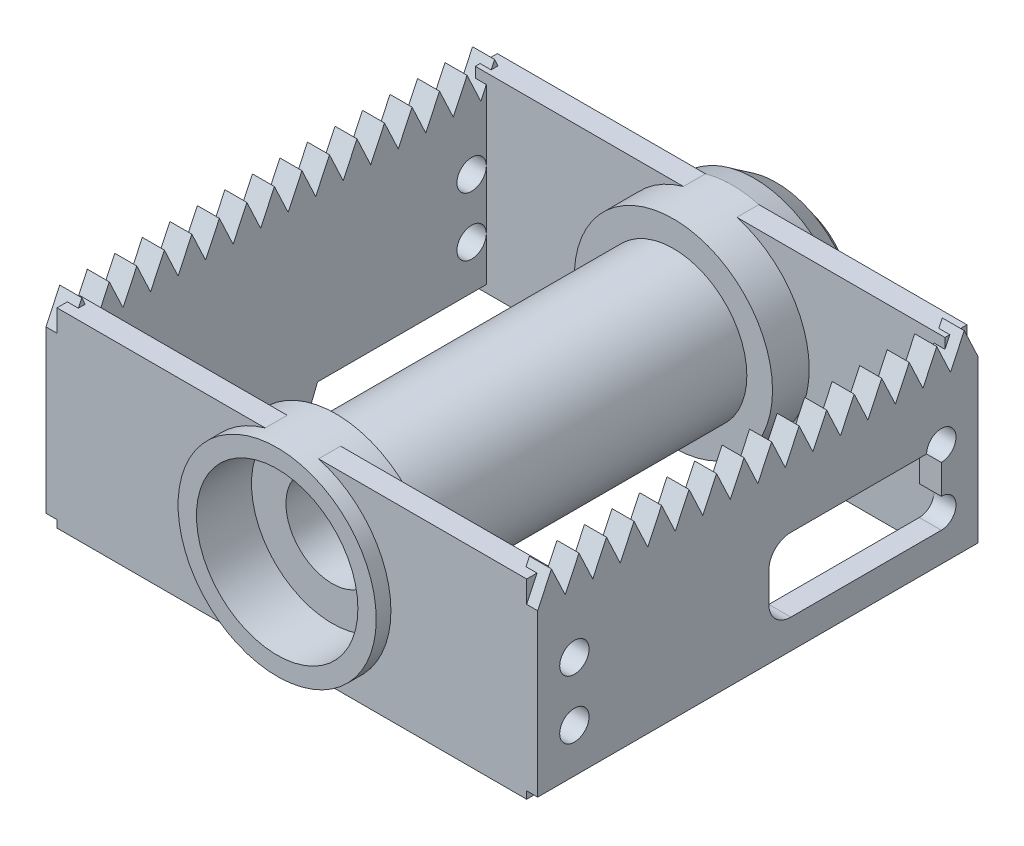
SolidWorks part; units mm, degrees
ref_plane "Alzado" through (0, 0, 0) normal (0, 0, 1) x (1, 0, 0)
ref_plane "Planta" through (0, 0, 0) normal (0, 1, 0) x (1, 0, 0)
ref_plane "Vista lateral" through (0, 0, 0) normal (1, 0, 0) x (0, 0, -1)
sketch "Sk_Eje_cuerpo" plane through (0, 0, 0) normal (0, 1, 0) x (1, 0, 0)
  line L0 (-183.5, 84) -> (-186, 84)
  line L1 (-186, 84) -> (-186, 92)
  line L2 (-186, 92) -> (-182.5, 92)
  line L3 (-182.5, 92) -> (-182.5, 138)
  line L4 (-182.5, 138) -> (-186, 138)
  line L5 (-186, 138) -> (-186, 146)
  line L6 (-186, 146) -> (-185.3, 149)
  line L7 (-185.3, 149) -> (-183.3, 152)
  line L8 (-183.3, 152) -> (-180, 154.5)
  line L9 (-180, 154.5) -> (-176.5, 155.7)
  line L10 (-176.5, 155.7) -> (-172.5, 156)
  line L11 (-172.5, 156) -> (-172.5, 147)
  line L12 (-172.5, 147) -> (-183.5, 147)
  line L13 (-183.5, 147) -> (-183.5, 138.5)
  line L14 (-183.5, 138.5) -> (-178.8, 138.5)
  line L15 (-178.8, 138.5) -> (-178.8, 91.5)
  line L16 (-178.8, 91.5) -> (-183.5, 91.5)
  line L17 (-183.5, 91.5) -> (-183.5, 84)
  line L18 (-172.5, 62.1) -> (-172.5, 160) construction
revolve "Eje_cuerpo" add sketch "Sk_Eje_cuerpo" angle 360 about L18
sketch "Sk_Placa_delantera" plane through (0, 0, 0) normal (1, 0, 0) x (0, 0, -1)
  line L0 (86, -12) -> (112, -12)
  line L1 (112, -12) -> (116, -22)
  line L2 (116, -22) -> (120, -12)
  line L3 (120, -12) -> (146, -12)
  line L4 (146, -12) -> (146, 10)
  line L5 (146, 10) -> (144.125, 14)
  line L6 (144.125, 14) -> (142.25, 10)
  line L7 (142.25, 10) -> (140.375, 14)
  line L8 (140.375, 14) -> (138.5, 10)
  line L9 (138.5, 10) -> (136.625, 14)
  line L10 (136.625, 14) -> (134.75, 10)
  line L11 (134.75, 10) -> (132.875, 14)
  line L12 (132.875, 14) -> (131, 10)
  line L13 (131, 10) -> (129.125, 14)
  line L14 (129.125, 14) -> (127.25, 10)
  line L15 (127.25, 10) -> (125.375, 14)
  line L16 (125.375, 14) -> (123.5, 10)
  line L17 (123.5, 10) -> (121.625, 14)
  line L18 (121.625, 14) -> (119.75, 10)
  line L19 (119.75, 10) -> (117.875, 14)
  line L20 (117.875, 14) -> (116, 10)
  line L21 (116, 10) -> (114.125, 14)
  line L22 (114.125, 14) -> (112.25, 10)
  line L23 (112.25, 10) -> (110.375, 14)
  line L24 (110.375, 14) -> (108.5, 10)
  line L25 (108.5, 10) -> (106.625, 14)
  line L26 (106.625, 14) -> (104.75, 10)
  line L27 (104.75, 10) -> (102.875, 14)
  line L28 (102.875, 14) -> (101, 10)
  line L29 (101, 10) -> (99.125, 14)
  line L30 (99.125, 14) -> (97.25, 10)
  line L31 (97.25, 10) -> (95.375, 14)
  line L32 (95.375, 14) -> (93.5, 10)
  line L33 (93.5, 10) -> (91.625, 14)
  line L34 (91.625, 14) -> (89.75, 10)
  line L35 (89.75, 10) -> (87.875, 14)
  line L36 (87.875, 14) -> (86, 10)
  line L37 (86, 10) -> (86, -12)
extrude "Placa_delantera" add sketch "Sk_Placa_delantera" along normal blind 3 from offset 206 offset against normal yes
sketch3d "Sk_Agujero_Placa_delantera_1"
  line L0 (-201.5, -6, -91) -> (-207.5, -6, -91)
  dimension "D1" = 6
sweep "Agujero_Placa_delantera_1" cut path "Sk_Agujero_Placa_delantera_1" circular profile diameter 4 parameters "D3"=4
sketch3d "Sk_Agujero_Placa_delantera_2"
  line L0 (-201.5, 2, -91) -> (-207.5, 2, -91)
  dimension "D1" = 6
sweep "Agujero_Placa_delantera_2" cut path "Sk_Agujero_Placa_delantera_2" circular profile diameter 4 parameters "D3"=4
sketch3d "Sk_Agujero_Placa_delantera_3"
  line L0 (-201.5, -6, -141) -> (-207.5, -6, -141)
  dimension "D1" = 6
sweep "Agujero_Placa_delantera_3" cut path "Sk_Agujero_Placa_delantera_3" circular profile diameter 4 parameters "D3"=4
sketch3d "Sk_Agujero_Placa_delantera_4"
  line L0 (-201.5, 2, -141) -> (-207.5, 2, -141)
  dimension "D1" = 6
sweep "Agujero_Placa_delantera_4" cut path "Sk_Agujero_Placa_delantera_4" circular profile diameter 4 parameters "D3"=4
sketch "Sk_Placa_trasera" plane through (0, 0, 0) normal (1, 0, 0) x (0, 0, -1)
  line L0 (86, -12) -> (146, -12)
  line L1 (146, -12) -> (146, 10)
  line L2 (146, 10) -> (144.125, 14)
  line L3 (144.125, 14) -> (142.25, 10)
  line L4 (142.25, 10) -> (140.375, 14)
  line L5 (140.375, 14) -> (138.5, 10)
  line L6 (138.5, 10) -> (136.625, 14)
  line L7 (136.625, 14) -> (134.75, 10)
  line L8 (134.75, 10) -> (132.875, 14)
  line L9 (132.875, 14) -> (131, 10)
  line L10 (131, 10) -> (129.125, 14)
  line L11 (129.125, 14) -> (127.25, 10)
  line L12 (127.25, 10) -> (125.375, 14)
  line L13 (125.375, 14) -> (123.5, 10)
  line L14 (123.5, 10) -> (121.625, 14)
  line L15 (121.625, 14) -> (119.75, 10)
  line L16 (119.75, 10) -> (117.875, 14)
  line L17 (117.875, 14) -> (116, 10)
  line L18 (116, 10) -> (114.125, 14)
  line L19 (114.125, 14) -> (112.25, 10)
  line L20 (112.25, 10) -> (110.375, 14)
  line L21 (110.375, 14) -> (108.5, 10)
  line L22 (108.5, 10) -> (106.625, 14)
  line L23 (106.625, 14) -> (104.75, 10)
  line L24 (104.75, 10) -> (102.875, 14)
  line L25 (102.875, 14) -> (101, 10)
  line L26 (101, 10) -> (99.125, 14)
  line L27 (99.125, 14) -> (97.25, 10)
  line L28 (97.25, 10) -> (95.375, 14)
  line L29 (95.375, 14) -> (93.5, 10)
  line L30 (93.5, 10) -> (91.625, 14)
  line L31 (91.625, 14) -> (89.75, 10)
  line L32 (89.75, 10) -> (87.875, 14)
  line L33 (87.875, 14) -> (86, 10)
  line L34 (86, 10) -> (86, -12)
extrude "Placa_trasera" add sketch "Sk_Placa_trasera" along normal blind 3 from offset 142 offset against normal yes
sketch3d "Sk_Agujero_Placa_trasera_1"
  line L0 (-137.5, -6, -91) -> (-143.5, -6, -91)
  dimension "D1" = 6
sweep "Agujero_Placa_trasera_1" cut path "Sk_Agujero_Placa_trasera_1" circular profile diameter 4 parameters "D3"=4
sketch3d "Sk_Agujero_Placa_trasera_2"
  line L0 (-137.5, 2, -91) -> (-143.5, 2, -91)
  dimension "D1" = 6
sweep "Agujero_Placa_trasera_2" cut path "Sk_Agujero_Placa_trasera_2" circular profile diameter 4 parameters "D3"=4
sketch3d "Sk_Agujero_Placa_trasera_3"
  line L0 (-137.5, -6, -141) -> (-143.5, -6, -141)
  dimension "D1" = 6
sweep "Agujero_Placa_trasera_3" cut path "Sk_Agujero_Placa_trasera_3" circular profile diameter 4 parameters "D3"=4
sketch3d "Sk_Agujero_Placa_trasera_4"
  line L0 (-137.5, 2, -141) -> (-143.5, 2, -141)
  dimension "D1" = 6
sweep "Agujero_Placa_trasera_4" cut path "Sk_Agujero_Placa_trasera_4" circular profile diameter 4 parameters "D3"=4
sketch "Sk_Marco_interior" plane through (0, 0, 0) normal (0, 0, 1) x (1, 0, 0)
  line L0 (-140.5, -13) -> (-204.5, -13)
  line L1 (-204.5, -13) -> (-204.5, 13)
  line L2 (-204.5, 13) -> (-140.5, 13)
  line L3 (-140.5, 13) -> (-140.5, -13)
  circle A0 centre (-172.5, 0) radius 11
  dimension "DIAM1" = 22
extrude "Marco_interior" add sketch "Sk_Marco_interior" along normal blind 3 from offset 89 offset against normal yes
sketch "Sk_Marco_exterior" plane through (0, 0, 0) normal (0, 0, 1) x (1, 0, 0)
  line L0 (-140.5, -13) -> (-204.5, -13)
  line L1 (-204.5, -13) -> (-204.5, 13)
  line L2 (-204.5, 13) -> (-140.5, 13)
  line L3 (-140.5, 13) -> (-140.5, -13)
  circle A0 centre (-172.5, 0) radius 11
  dimension "DIAM2" = 22
extrude "Marco_exterior" add sketch "Sk_Marco_exterior" along normal blind 3 from offset 146 offset against normal yes
ref_axis "Eje_pedal" through (-172.5, 0, -146) along (0, 0, 1)
sketch "Croquis1" plane through (-139, 0, 0) normal (1, 0, 0) x (0, 0, -1)
  line L0 (117.492, -1) -> (117.492, -5)
  line L1 (120.492, -8) -> (141, -8)
  line L2 (141, -8) -> (141, 2)
  line L3 (141, 2) -> (120.492, 2)
  circle A0 centre (141, -6) radius 2 construction
  arc A1 (117.492, -1) -> (120.492, 2) centre (120.492, -1) cw
  arc A2 (117.492, -5) -> (120.492, -8) centre (120.492, -5) ccw
  dimension "D1" = 3
extrude "Cortar-Extruir2" cut sketch "Croquis1" against normal blind 10
